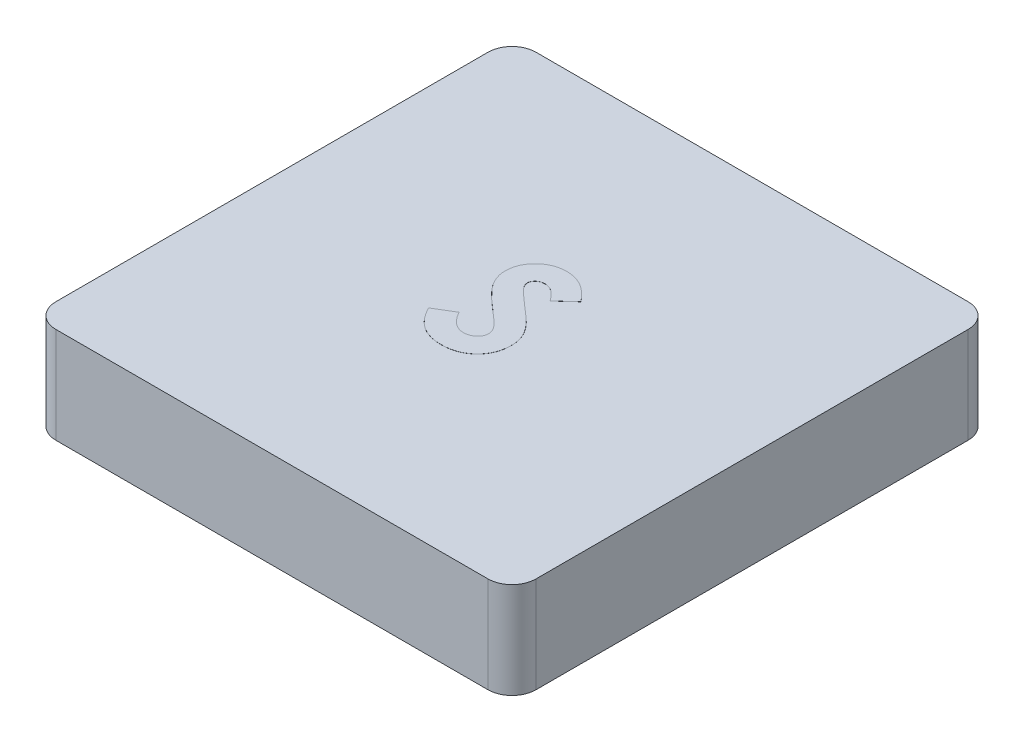
SolidWorks part; units mm, degrees
ref_plane "Front Plane" through (0, 0, 0) normal (0, 0, 1) x (1, 0, 0)
ref_plane "Top Plane" through (0, 0, 0) normal (0, 1, 0) x (1, 0, 0)
ref_plane "Right Plane" through (0, 0, 0) normal (1, 0, 0) x (0, 0, -1)
sketch "Sketch1" plane through (0, 0, 0) normal (0, 1, 0) x (1, 0, 0)
  line L0 (0, 0) -> (12.7, 0)
  line L1 (12.7, 0) -> (12.7, 12.7)
  line L2 (12.7, 12.7) -> (0, 12.7)
  line L3 (0, 12.7) -> (0, 0)
  dimension "D1" = 12.7
  dimension "D2" = 12.7
extrude "Boss-Extrude1" add sketch "Sketch1" along normal blind 2.54
fillet "Fillet1" radius 0.635 4 edges at (0, 1.27, -12.7) (12.7, 1.27, -12.7) (12.7, 1.27, 0) (0, 1.27, 0)
shell "Shell1" thickness 0.635 removed face at (6.35, 0, -6.35)
sketch "Sketch2" plane through (0, 1.905, 0) normal (0, -1, 0) x (-1, 0, 0)
  line L0 (-0.635, 6.35) -> (-12.065, 6.35) construction
  line L1 (-0.635, 12.065) -> (-0.635, 0.635) construction
  line L2 (-12.065, 0.635) -> (-12.065, 12.065) construction
  line L3 (-6.35, 0.635) -> (-6.35, 12.065) construction
  line L4 (-0.635, 0.635) -> (-12.065, 0.635) construction
  line L5 (-12.065, 12.065) -> (-0.635, 12.065) construction
  circle A0 centre (-6.35, 6.35) radius 2.54
  dimension "D1" = 5.08
extrude "Boss-Extrude2" add sketch "Sketch2" along normal up to surface (1.905 mm away) up to face at (6.35, 0, -6.35)
sketch "Sketch3" plane through (0, 2.54, 0) normal (0, 1, 0) x (1, 0, 0)
  line L0 (0, 12.065) -> (0, 0.635) construction
  line L1 (0.635, 0) -> (12.065, 0) construction
  text T0 "<b>S</b>"
  point P1 (0, 0)
  dimension "D1" = 4.953
  dimension "D2" = 4.826
extrude "Boss-Extrude3" add sketch "Sketch3" along normal blind 0.0025
